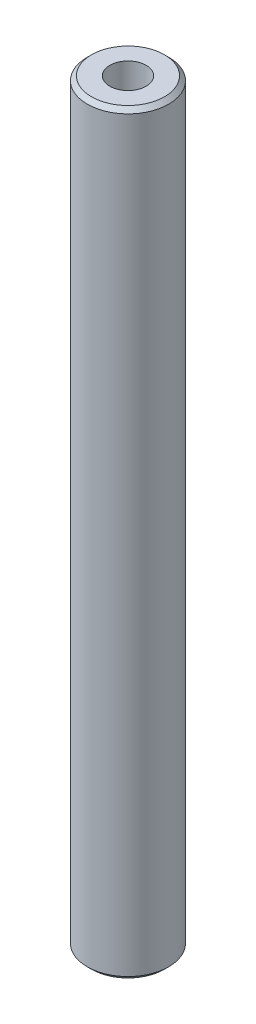
SolidWorks part; units mm, degrees
ref_plane "Front Plane" through (0, 0, 0) normal (0, 0, 1) x (1, 0, 0)
ref_plane "Top Plane" through (0, 0, 0) normal (0, 1, 0) x (1, 0, 0)
ref_plane "Right Plane" through (0, 0, 0) normal (1, 0, 0) x (0, 0, -1)
sketch "Sketch1" plane through (0, 0, 0) normal (0, 1, 0) x (1, 0, 0)
  circle A0 centre (0, 0) radius 7.5
  dimension "SHAFT_OD" = 15
extrude "Boss-Extrude1" add sketch "Sketch1" along normal blind 139.2005
sketch "Sketch2" plane through (0, 0, 0) normal (0, 1, 0) x (1, 0, 0)
  circle A0 centre (0, 0) radius 3.3486
  dimension "BORE_D" = 6.6973
extrude "Cut-Extrude1" cut sketch "Sketch2" along normal through all
chamfer "Chamfer1" distance 0.7824 angle 45 2 edges at (0, 139.2005, 7.5) (0, 0, 7.5)
